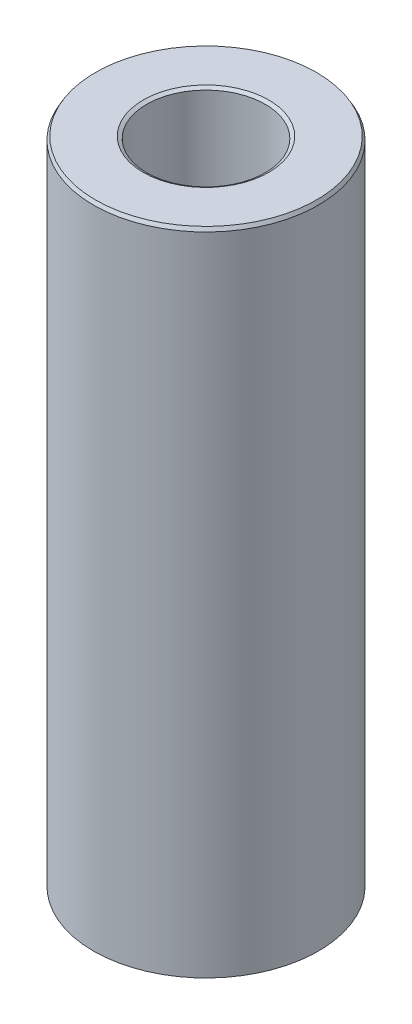
SolidWorks part; units mm, degrees
ref_plane "Front Plane" through (0, 0, 0) normal (0, 0, 1) x (1, 0, 0)
ref_plane "Top Plane" through (0, 0, 0) normal (0, 1, 0) x (1, 0, 0)
ref_plane "Right Plane" through (0, 0, 0) normal (1, 0, 0) x (0, 0, -1)
sketch "Sketch1" plane through (0, 0, 0) normal (0, 1, 0) x (1, 0, 0)
  circle A0 centre (0, 0) radius 45
  dimension "SLEEVE_OD" = 90
extrude "Boss-Extrude1" add sketch "Sketch1" along normal blind 260.6311
sketch "Sketch2" plane through (0, 0, 0) normal (0, 1, 0) x (1, 0, 0)
  circle A0 centre (0, 0) radius 23.73
  dimension "BORE_D" = 47.46
extrude "Cut-Extrude1" cut sketch "Sketch2" along normal through all
chamfer "Chamfer1" distance 1.3818 angle 30 4 edges at (0, 260.6311, 23.73) (0, 0, 23.73) (0, 0, 45) (0, 260.6311, 45) first distance on face at (0, 260.6311, 23.73) first distance on face at (0, 0, 23.73) first distance on face at (0, 260.6311, 45)
